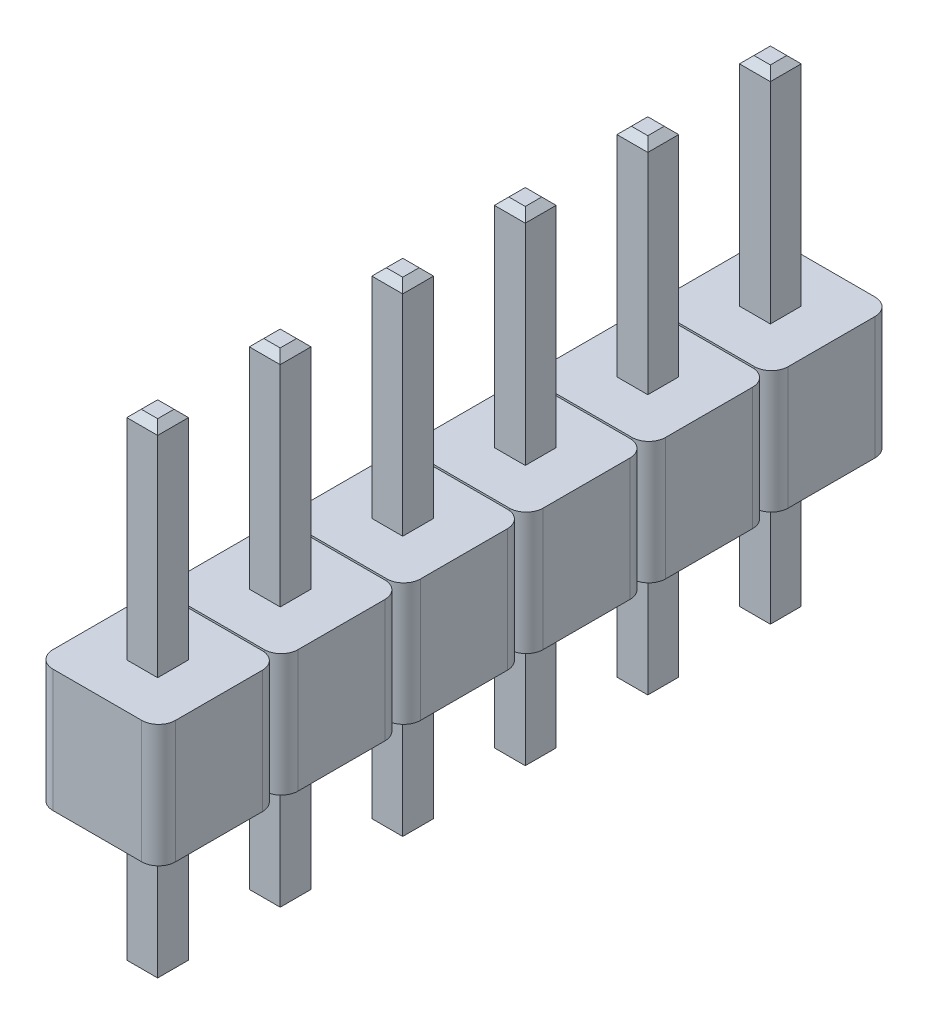
SolidWorks part; units mm, degrees
ref_plane "Front Plane" through (0, 0, 0) normal (0, 0, 1) x (1, 0, 0)
ref_plane "Top Plane" through (0, 0, 0) normal (0, 1, 0) x (1, 0, 0)
ref_plane "Right Plane" through (0, 0, 0) normal (1, 0, 0) x (0, 0, -1)
sketch "Sketch1" plane through (0, 0, 0) normal (0, 1, 0) x (1, 0, 0)
  line L1 (0, 0) -> (0.64, 0)
  line L2 (0, 0) -> (0, 0.64)
  line L3 (0, 0.64) -> (0.64, 0.64)
  line L4 (0.64, 0) -> (0.64, 0.64)
  dimension "D1" = 0.64
  dimension "D2" = 0.64
extrude "Boss-Extrude1" add sketch "Sketch1" along normal blind 10.04
chamfer "Chamfer1" distance 0.15 angle 45 8 edges at (0.32, 0, 0) (0.64, 0, -0.32) (0.32, 0, -0.64) (0, 0, -0.32) (0.32, 10.04, -0.64) (0.64, 10.04, -0.32) (0.32, 10.04, 0) (0, 10.04, -0.32)
ref_plane "Plane1" through (0, 5.54, 0) normal (0, 1, 0) x (1, 0, 0)
sketch "Sketch3" plane through (0, 5.54, 0) normal (0, 1, 0) x (1, 0, 0)
  line L0 (0.32, 0.64) -> (0.32, 0) construction
  line L1 (0, 0.64) -> (0.64, 0.64) construction
  line L2 (0.64, 0) -> (0, 0) construction
  line L4 (-0.6, -0.93) -> (1.24, -0.93)
  line L5 (-0.95, -0.58) -> (-0.95, 1.22)
  line L6 (-0.6, 1.57) -> (1.24, 1.57)
  line L7 (1.59, -0.58) -> (1.59, 1.22)
  line L8 (-0.95, -0.93) -> (1.59, 1.57) construction
  line L9 (-0.95, 1.57) -> (1.59, -0.93) construction
  arc A0 (-0.6, -0.93) -> (-0.95, -0.58) centre (-0.6, -0.58) cw
  arc A1 (1.24, 1.57) -> (1.59, 1.22) centre (1.24, 1.22) cw
  arc A2 (-0.95, 1.22) -> (-0.6, 1.57) centre (-0.6, 1.22) cw
  arc A3 (1.24, -0.93) -> (1.59, -0.58) centre (1.24, -0.58) ccw
  point P6 (0.32, 0.32)
  point P7 (0.32, 0.32)
  dimension "D3" = 0.35
  dimension "D1" = 2.5
  dimension "D2" = 2.54
extrude "Boss-Extrude2" add sketch "Sketch3" against normal blind 2.54
ref_axis "Axis1" through (0.32, 3, 0.93) along (0, 0, -1)
pattern_linear "LPattern2" count 6 spacing 2.54 along (0, 0, -1) of bodies 102
